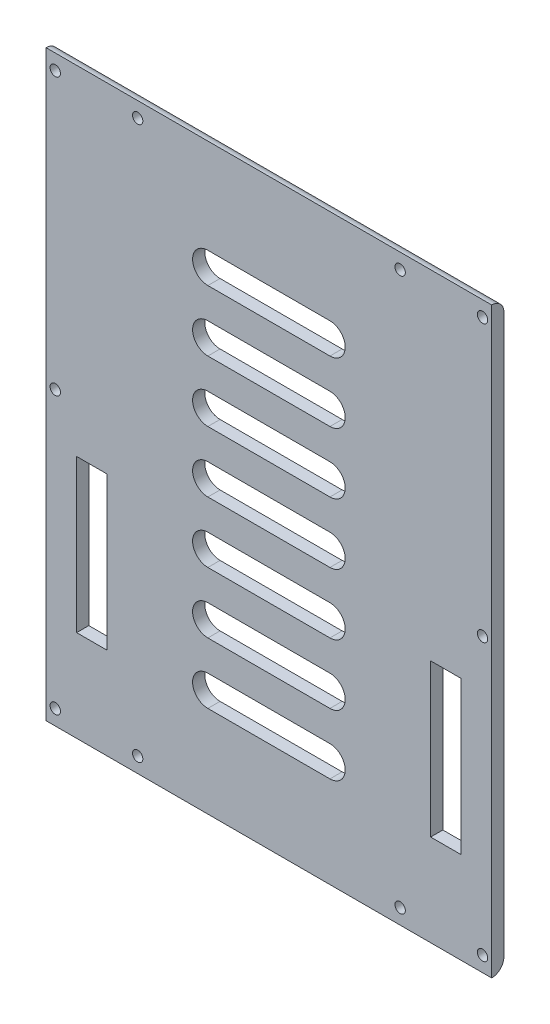
SolidWorks part; units mm, degrees
ref_plane "Front Plane" through (0, 0, 0) normal (1, 0, 0) x (0, 1, 0)
ref_plane "Top Plane" through (0, 0, 0) normal (0, 0, 1) x (0, 1, 0)
ref_plane "Right Plane" through (0, 0, 0) normal (0, 1, 0) x (-1, 0, 0)
sketch "Sketch1" plane through (0, 0, 0) normal (0, 0, 1) x (0, 1, 0)
  line L0 (95.5, 146) -> (95.5, 0) construction
  line L1 (0, 0) -> (191, 0)
  line L2 (0, 0) -> (0, 146)
  line L3 (0, 146) -> (191, 146)
  line L4 (191, 0) -> (191, 146)
  line L5 (35, 93) -> (35, 53) construction
  line L6 (30, 136) -> (80, 136)
  line L7 (30, 136) -> (30, 126)
  line L8 (30, 126) -> (80, 126)
  line L9 (80, 136) -> (80, 126)
  line L10 (30, 20) -> (80, 20)
  line L11 (30, 20) -> (30, 10)
  line L12 (30, 10) -> (80, 10)
  line L13 (80, 20) -> (80, 10)
  line L14 (40, 93) -> (40, 53)
  line L15 (30, 93) -> (30, 53)
  line L16 (0, 73) -> (191, 73) construction
  line L17 (55, 93) -> (55, 53) construction
  line L18 (60, 93) -> (60, 53)
  line L19 (50, 93) -> (50, 53)
  line L20 (75, 93) -> (75, 53) construction
  line L21 (80, 93) -> (80, 53)
  line L22 (70, 93) -> (70, 53)
  line L23 (95, 93) -> (95, 53) construction
  line L24 (100, 93) -> (100, 53)
  line L25 (90, 93) -> (90, 53)
  line L26 (115, 93) -> (115, 53) construction
  line L27 (120, 93) -> (120, 53)
  line L28 (110, 93) -> (110, 53)
  line L29 (135, 93) -> (135, 53) construction
  line L30 (140, 93) -> (140, 53)
  line L31 (130, 93) -> (130, 53)
  line L32 (155, 93) -> (155, 53) construction
  line L33 (160, 93) -> (160, 53)
  line L34 (150, 93) -> (150, 53)
  circle A0 centre (5, 3) radius 1.7
  circle A1 centre (5, 143) radius 1.7
  circle A2 centre (186, 143) radius 1.7
  circle A3 centre (186, 3) radius 1.7
  circle A4 centre (95.5, 143) radius 1.7
  circle A5 centre (95.5, 3) radius 1.7
  arc A6 (40, 93) -> (30, 93) centre (35, 93) ccw
  arc A7 (30, 53) -> (40, 53) centre (35, 53) ccw
  arc A8 (60, 93) -> (50, 93) centre (55, 93) ccw
  arc A9 (50, 53) -> (60, 53) centre (55, 53) ccw
  arc A10 (80, 93) -> (70, 93) centre (75, 93) ccw
  arc A11 (70, 53) -> (80, 53) centre (75, 53) ccw
  arc A12 (100, 93) -> (90, 93) centre (95, 93) ccw
  arc A13 (90, 53) -> (100, 53) centre (95, 53) ccw
  arc A14 (120, 93) -> (110, 93) centre (115, 93) ccw
  arc A15 (110, 53) -> (120, 53) centre (115, 53) ccw
  arc A16 (140, 93) -> (130, 93) centre (135, 93) ccw
  arc A17 (130, 53) -> (140, 53) centre (135, 53) ccw
  arc A18 (160, 93) -> (150, 93) centre (155, 93) ccw
  arc A19 (150, 53) -> (160, 53) centre (155, 53) ccw
  circle A20 centre (5, 30) radius 1.7
  circle A21 centre (186, 30) radius 1.7
  circle A22 centre (186, 116) radius 1.7
  circle A23 centre (5, 116) radius 1.7
  point P29 (35, 73)
  point P37 (0, 73)
  point P41 (55, 73)
  point P48 (75, 73)
  point P55 (95, 73)
  point P62 (115, 73)
  point P69 (135, 73)
  point P76 (155, 73)
  point P87 (0, 0)
  point P88 (0, 0)
  point P89 (0, 0)
  point P90 (0, 0)
  point P91 (5, 61.5293)
  point P92 (0, 0)
  point P93 (0, 0)
  dimension "D7" = 3.4
  dimension "D1" = 191
  dimension "D2" = 146
  dimension "D3" = 3
  dimension "D4" = 5
  dimension "D5" = 3
  dimension "D6" = 5
  dimension "D8" = 30
  dimension "D9" = 10
  dimension "D10" = 10
  dimension "D11" = 10
  dimension "D12" = 50
  dimension "D13" = 10
  dimension "D14" = 40
  dimension "D16" = 10
  dimension "D17" = 10
  dimension "D15" = 7
extrude "Boss-Extrude2" add sketch "Sketch1" along normal blind 4
fillet "Fillet1" radius 4 2 edges at (-73, 191, 0) (-73, 0, 0)
equation "\"MotorDriverLength\"= 60mm"
equation "\"MotorLength\"= 60"
equation "\"MotorDriverWidth\"=45"
equation "\"MotorWidth\"= 37"
equation "\"InnerWallThickness\"=3"
equation "\"BatteryWidth\"= 60"
equation "\"OuterWallThickness\" = 6"
equation "\"CompartmentHeight\"=37"
equation "\"CompartmentWidth\"= \"MotorDriverLength\""
equation "\"MotorDiameter\"=37"
equation "\"BatteryHeight\"=24.2019"
equation "\"MotorDriverHeight\"=20"
equation "\"CircuitHeight\"=30"
equation "\"FanThickness\"= 10"
equation "\"FanHeight\"=50"
equation "\"MotorShaftHole\"=12"
equation "\"BearingBore\"=4"
equation "\"MinShinWidth\"= 20"
equation "\"ShinThickness\"=10"
equation "\"PivotDistance\"=40"
equation "\"ThighLength\"= 200"
equation "\"KneeLength\" =20"
equation "\"HipBore\"=27"
equation "\"ThighThickness\"=20"
equation "\"MaxBending\"=135"
equation "\"MaxStretchingAngle\"= 140"
equation "\"ThighJointDistance\"=157.485"
equation "\"ShinLength\"=100"
equation "\"BearingDiameter\"= 10"
equation "\"CircuitLength\"=50"
equation "\"ChessisInnerWidth\"= \"OuterWallThickness\" * 2 + \"MotorDriverLength\" * 2 + \"InnerWallThickness\" * 3 + \"CircuitLength\""
equation "\"D1@Sketch1\"=\"ChessisInnerWidth\""
equation "\"D2@Sketch1\"=\"MotorLength\"*2 + 20 +\"InnerWallThickness\"*2"
